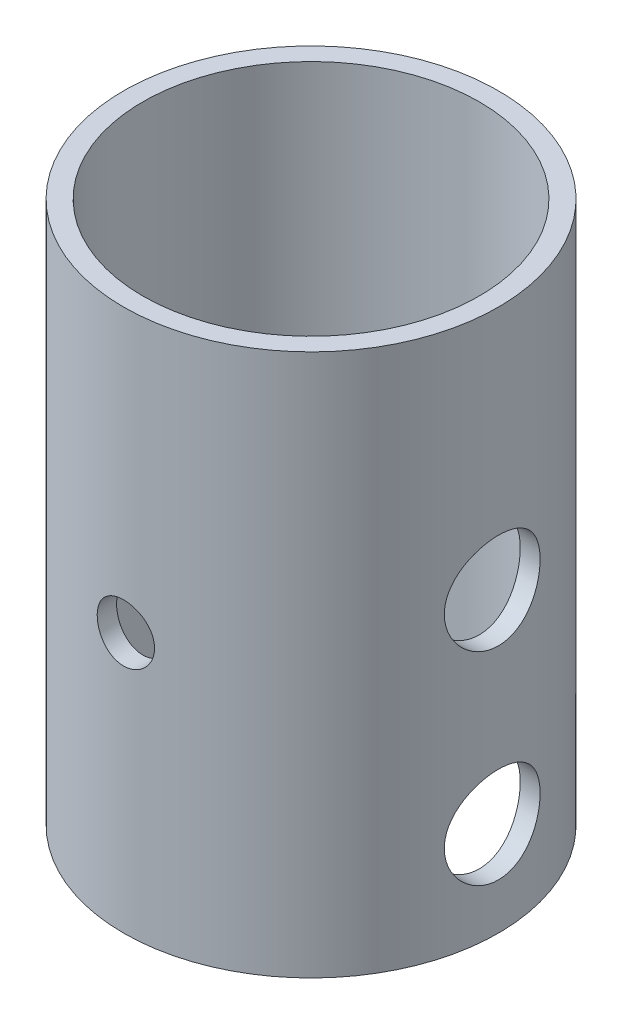
SolidWorks part; units mm, degrees
material "PTFE (general)"
ref_plane "Front Plane" through (0, 0, 0) normal (0, 0, 1) x (1, 0, 0)
ref_plane "Top Plane" through (0, 0, 0) normal (0, 1, 0) x (1, 0, 0)
ref_plane "Right Plane" through (0, 0, 0) normal (1, 0, 0) x (0, 0, -1)
sketch "Sketch1" plane through (0, 0, 0) normal (0, 1, 0) x (1, 0, 0)
  circle A0 centre (0, 0) radius 49
  circle A1 centre (0, 0) radius 44
  dimension "D1" = 98
  dimension "D2" = 88
extrude "Boss-Extrude1" add sketch "Sketch1" along normal blind 141.8
sketch "Sketch2" plane through (0, 0, 0) normal (1, 0, 0) x (0, 0, -1)
  line L1 (49, 141.8) -> (-49, 141.8) construction
  circle A0 centre (0, 24.6) radius 12.53
  circle A1 centre (0, 77.6) radius 12.53
  dimension "D2" = 25.06
  dimension "D3" = 25.06
  dimension "D1" = 64.2
  dimension "D5" = 53
extrude "Cut-Extrude1" cut sketch "Sketch2" along normal through all
sketch "Sketch4" plane through (0, 0, 0) normal (0, 0, 1) x (1, 0, 0)
  line L0 (-49, 0) -> (49, 0) construction
  circle A0 centre (0, 68) radius 7.5
  dimension "D1" = 15
  dimension "D2" = 68
extrude "Cut-Extrude2" cut sketch "Sketch4" along normal through all
sketch "Sketch5" plane through (0, 0, 0) normal (0, 0, 1) x (1, 0, 0)
  line L0 (49, 141.8) -> (-49, 141.8) construction
  circle A0 centre (0, 73.8) radius 7.5
  dimension "D1" = 15
  dimension "D2" = 68
extrude "Cut-Extrude3" cut sketch "Sketch5" against normal through all
